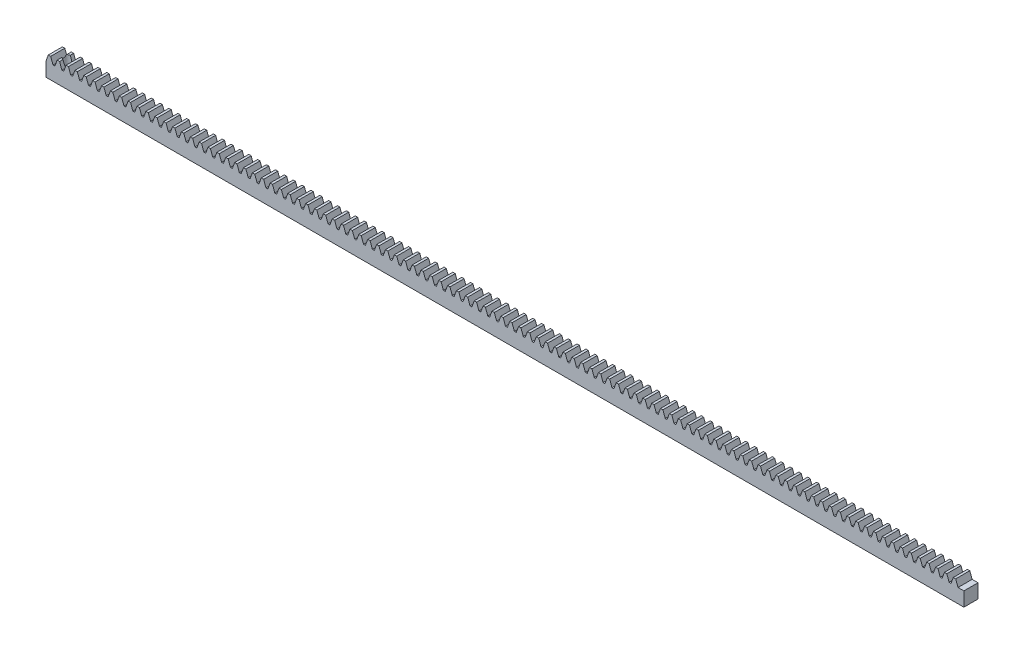
SolidWorks part; units mm, degrees
ref_plane "前视基准面" through (0, 0, 0) normal (0, 0, 1) x (1, 0, 0)
ref_plane "上视基准面" through (0, 0, 0) normal (0, 1, 0) x (1, 0, 0)
ref_plane "右视基准面" through (0, 0, 0) normal (1, 0, 0) x (0, 0, -1)
sketch "草图1" plane through (0, 0, 0) normal (0, 0, 1) x (1, 0, 0)
  line L1 (0, 0) -> (650, 0)
  line L2 (0, 0) -> (0, -10)
  line L3 (0, -10) -> (650, -10)
  line L4 (650, 0) -> (650, -10)
  dimension "D1" = 10
  dimension "L" = 650
extrude "拉伸1" add sketch "草图1" along normal blind 10
sketch "草图2" plane through (0, 0, 10) normal (0, 0, 1) x (1, 0, 0)
  line L0 (0, 0) -> (1.6379, 4.5)
  line L1 (1.6379, 4.5) -> (3.3236, 4.5)
  line L2 (3.3236, 4.5) -> (4.9614, 0)
  line L3 (650, 0) -> (0, 0) construction
  line L4 (0, 0) -> (4.9614, 0)
  line L5 (0.9099, 2.5) -> (4.0515, 2.5) construction
  dimension "D2" = 70
  dimension "alpha" = 110
  dimension "ha" = 2
  dimension "hf" = 2.5
  dimension "S" = 3.1416
extrude "拉伸2" add sketch "草图2" against normal up to surface (10 mm away) up to face at (325, -5, 0)
pattern_linear "阵列(线性)1" count 103 spacing 6.2832 along (1, 0, 0) of "拉伸2"
sketch "草图3" plane through (0, -10, 0) normal (0, -1, 0) x (1, 0, 0)
  line L0 (0, 5) -> (26.9765, 5) construction
  line L1 (0, 10) -> (0, 0) construction
  circle A0 centre (10, 5) radius 2.6
  point P6 (10.1682, 5)
  dimension "D2" = 5.2
  dimension "D1" = 10
extrude "切除-拉伸1" cut sketch "草图3" against normal up to next
equation "\"d\"=\"S@草图2\" * 2"
equation "\"z\"= int(  \"L@草图1\" / (  \"S@草图2\" * 2 ) + 0.5 )"
